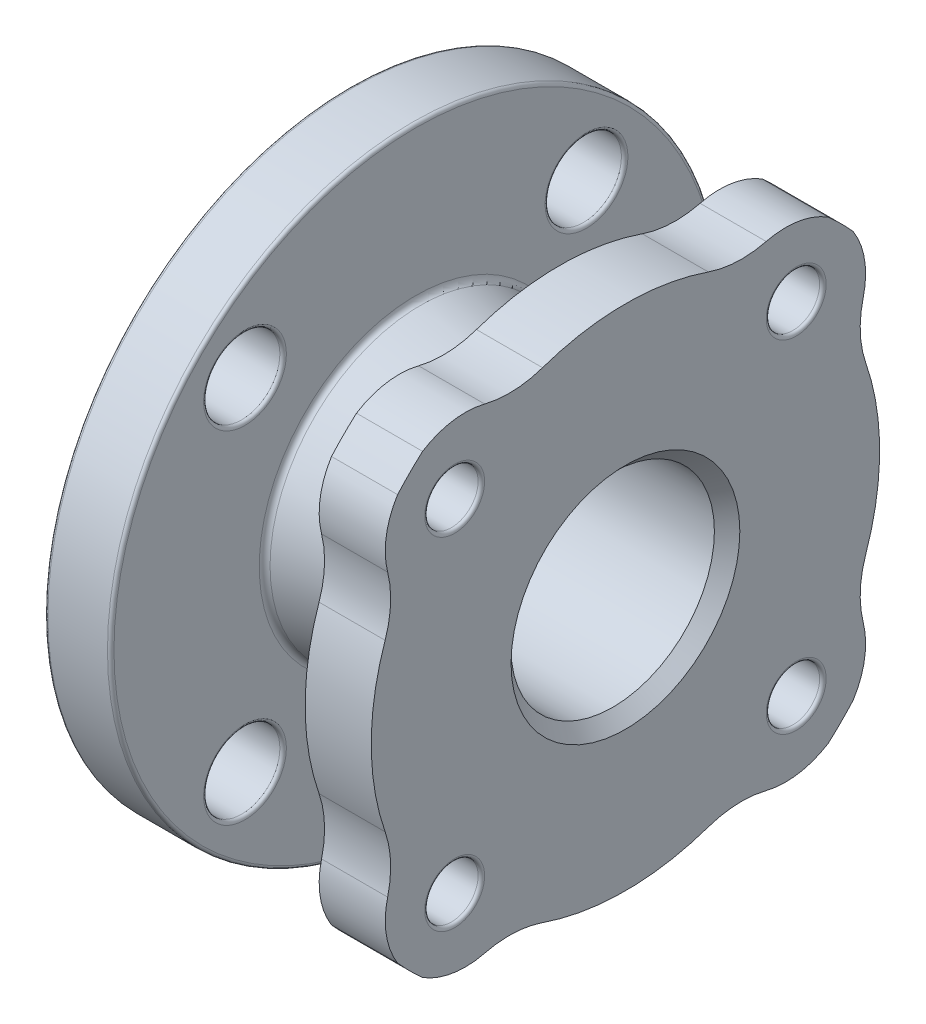
SolidWorks part; units mm, degrees
ref_plane "Front Plane" through (0, 0, 0) normal (0, 0, 1) x (1, 0, 0)
ref_plane "Top Plane" through (0, 0, 0) normal (0, 1, 0) x (1, 0, 0)
ref_plane "Right Plane" through (0, 0, 0) normal (1, 0, 0) x (0, 0, -1)
sketch "Sketch2" plane through (0, 0, 0) normal (0, 0, 1) x (1, 0, 0)
  line L0 (-79.0015, 0) -> (88.7132, 0) construction
  line L1 (-20.1706, -25.4) -> (50.3144, -25.4)
  line L2 (50.3144, -25.4) -> (50.3144, -55.4691)
  line L3 (50.3144, -55.4691) -> (33.8044, -55.4691)
  line L4 (33.8044, -55.4691) -> (33.8044, -47.625)
  line L6 (32.2042, -34.29) -> (14.7544, -34.29)
  line L7 (14.7544, -34.29) -> (-2.0604, -37.8641)
  line L8 (-2.0604, -37.8641) -> (-2.0604, -76.2)
  line L9 (-2.0604, -76.2) -> (-18.5704, -76.2)
  line L10 (-18.5704, -76.2) -> (-18.5704, -47.6377)
  line L13 (33.8044, -47.625) -> (32.2042, -46.0248)
  line L14 (32.2042, -46.0248) -> (32.2042, -34.29)
  line L15 (-18.5704, -47.6377) -> (-20.1706, -46.0375)
  line L16 (-20.1706, -46.0375) -> (-20.1706, -25.4)
  dimension "D1" = 50.8
  dimension "D2" = 68.58
  dimension "D3" = 95.25
  dimension "D4" = 16.51
  dimension "D5" = 1.6002
  dimension "D6" = 45
  dimension "D7" = 45
  dimension "D8" = 16.51
  dimension "D9" = 34.925
  dimension "D10" = 12
  dimension "D11" = 53.975
  dimension "D12" = 92.075
  dimension "D13" = 152.4
  dimension "D14" = 1.6002
revolve "Revolve1" add sketch "Sketch2" angle 360 about L0
sketch "Sketch3" plane through (50.3144, 0, 0) normal (1, 0, 0) x (0, 0, -1)
  line L0 (0, 73.6441) -> (0, -80.5557) construction
  line L1 (0, 0) -> (-51.6043, 51.6043) construction
  line L2 (-80.6749, 0) -> (83.7732, 0) construction
  circle A0 centre (0, 0) radius 60.325 construction
  arc A1 (-60.0279, 20.71) -> (-60.0279, -20.71) centre (0, 0) ccw
  circle A2 centre (0, 0) radius 76.2
  arc A3 (-35.1558, 59.3977) -> (-59.3977, 35.1558) centre (-40.005, 40.005) ccw
  arc A4 (35.1558, 59.3977) -> (59.3977, 35.1558) centre (40.005, 40.005) cw
  arc A5 (35.1558, -59.3977) -> (59.3977, -35.1558) centre (40.005, -40.005) ccw
  arc A6 (-35.1558, -59.3977) -> (-59.3977, -35.1558) centre (-40.005, -40.005) cw
  arc A7 (-60.0279, 20.71) -> (-59.3977, 35.1558) centre (-84.039, 28.9941) ccw
  arc A8 (-20.71, 60.0279) -> (-35.1558, 59.3977) centre (-28.9941, 84.039) cw
  arc A9 (-60.0279, -20.71) -> (-59.3977, -35.1558) centre (-84.039, -28.9941) cw
  arc A10 (-20.71, -60.0279) -> (-35.1558, -59.3977) centre (-28.9941, -84.039) ccw
  arc A11 (60.0279, -20.71) -> (59.3977, -35.1558) centre (84.039, -28.9941) ccw
  arc A12 (20.71, -60.0279) -> (35.1558, -59.3977) centre (28.9941, -84.039) cw
  arc A13 (60.0279, 20.71) -> (59.3977, 35.1558) centre (84.039, 28.9941) cw
  arc A14 (20.71, 60.0279) -> (35.1558, 59.3977) centre (28.9941, 84.039) ccw
  arc A15 (20.71, 60.0279) -> (-20.71, 60.0279) centre (0, 0) ccw
  arc A16 (60.0279, -20.71) -> (60.0279, 20.71) centre (0, 0) ccw
  arc A17 (-20.71, -60.0279) -> (20.71, -60.0279) centre (0, 0) ccw
  circle A19 centre (-42.6562, 42.6562) radius 6.6675
  circle A20 centre (42.6562, 42.6562) radius 6.6675
  circle A21 centre (42.6562, -42.6562) radius 6.6675
  circle A22 centre (-42.6562, -42.6562) radius 6.6675
  circle M5 centre (0, 0) radius 55.4691
  dimension "D1" = 120.65
  dimension "D2" = 127
  dimension "D3" = 45
  dimension "D5" = 39.9796
  dimension "D6" = 152.4
  dimension "D7" = 39.9796
  dimension "D8" = 13.335
  dimension "D4" = 40.005
extrude "Boss-Extrude1" add sketch "Sketch3" against normal blind 16.51 contours A10 A17 A12 A5 A2 A11 A16 A13 A4 A14 A15 A8 A3 A7 A1 A9 A6 M5 region at (50.3144, 27.8088, 56.8688)
extrude "Cut-Extrude1" cut sketch "Sketch3<3>" against normal through all contours A19 M5 | A20 M5 | A21 M5 | A22 M5 region at (50.3144, 38.6798, 38.6798) region at (50.3144, -38.6798, 38.6798) region at (50.3144, 38.6798, -38.6798) region at (50.3144, -38.6798, -38.6798)
sketch "Sketch3<3>" plane through (50.3144, 0, 0) normal (1, 0, 0) x (0, 0, -1) same geometry as "Sketch3"
fillet "Fillet1" radius 1.524 2 edges at (32.2042, 0, 34.29) (-2.0604, 0, 37.8641)
chamfer "Chamfer1" distance 3.175 angle 45 2 edges at (50.3144, 0, 25.4) (-20.1706, 0, 25.4)
sketch "Sketch4" plane through (-18.5704, 0, 0) normal (-1, 0, 0) x (0, 0, 1)
  line L0 (0, 0) -> (0, 70.274) construction
  line L1 (0, 70.274) -> (0, 0) construction
  line L2 (0, 0) -> (-86.1761, 0) construction
  line L3 (-86.1761, 0) -> (0, 0) construction
  line L4 (0, 0) -> (-48.7028, 48.7028) construction
  circle A0 centre (0, 0) radius 60.325 construction
  circle A1 centre (-42.6562, 42.6562) radius 9.525
  circle A2 centre (42.6562, 42.6562) radius 9.525
  circle A3 centre (42.6562, -42.6562) radius 9.525
  circle A4 centre (-42.6562, -42.6562) radius 9.525
  dimension "D2" = 120.65
  dimension "D1" = 45
extrude "Cut-Extrude2" cut sketch "Sketch4" against normal up to next
fillet "Fillet2" radius 0.8128 18 edges at (33.8044, -42.6562, -49.3237) (50.3144, -42.6562, -49.3237) (33.8044, -42.6562, 35.9887) (50.3144, -42.6562, 35.9887) (33.8044, 42.6562, 35.9887) (50.3144, 42.6562, 35.9887) (33.8044, 42.6562, -49.3237) (50.3144, 42.6562, -49.3237) (-18.5704, -42.6562, 52.1812) (-2.0604, -42.6562, 33.1312) (-18.5704, -42.6562, -33.1312) (-2.0604, -42.6562, -52.1812) (-18.5704, 42.6562, 52.1812) (-2.0604, 42.6562, 33.1312) (-18.5704, 42.6562, -33.1312) (-2.0604, 42.6562, -52.1812) (-18.5704, 0, 76.2) (-2.0604, 0, 76.2)
